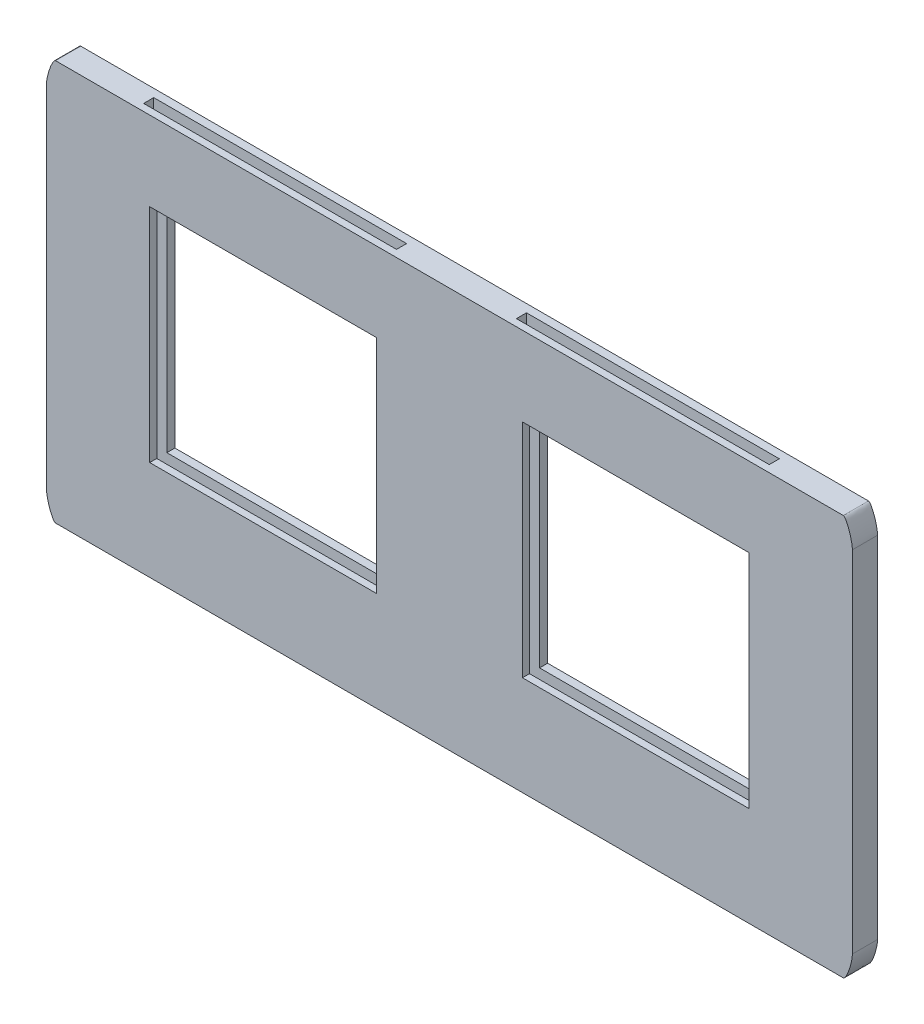
SolidWorks part; units mm, degrees
ref_plane "前视基准面" through (0, 0, 0) normal (0, 0, 1) x (1, 0, 0)
ref_plane "上视基准面" through (0, 0, 0) normal (0, 1, 0) x (1, 0, 0)
ref_plane "右视基准面" through (0, 0, 0) normal (1, 0, 0) x (0, 0, -1)
sketch "草图1" plane through (0, 0, 0) normal (0, 0, 1) x (1, 0, 0)
  line L1 (-80, 39.75) -> (80, 39.75)
  line L2 (-80, 39.75) -> (-80, -39.75)
  line L3 (-80, -39.75) -> (80, -39.75)
  line L4 (80, 39.75) -> (80, -39.75)
  line L5 (-80, 39.75) -> (80, -39.75) construction
  line L6 (-80, -39.75) -> (80, 39.75) construction
  point P0 (0, 0)
  dimension "D1" = 160
  dimension "D2" = 79.5
extrude "凸台-拉伸1" add sketch "草图1" along normal mid plane 5
sketch "草图2" plane through (0, 0, 2.5) normal (0, 0, 1) x (1, 0, 0)
  line L0 (0, 0) -> (0, -20.626) construction
  line L1 (-55, 12) -> (-19, 12) construction
  line L2 (-55, 12) -> (-55, -12) construction
  line L3 (-55, -12) -> (-19, -12) construction
  line L4 (-19, 12) -> (-19, -12) construction
  line L5 (-55, 12) -> (-19, -12) construction
  line L6 (-55, -12) -> (-19, 12) construction
  line L7 (55, -12) -> (19, 12) construction
  line L8 (55, 12) -> (19, -12) construction
  line L9 (19, 12) -> (19, -12) construction
  line L10 (55, -12) -> (19, -12) construction
  line L11 (55, 12) -> (55, -12) construction
  line L12 (55, 12) -> (19, 12) construction
  line L13 (-80, 39.75) -> (-80, -39.75) construction
  line L15 (-62, 25) -> (-12, 25) construction
  line L16 (-62, 25) -> (-62, -25) construction
  line L17 (-62, -25) -> (-12, -25) construction
  line L18 (-12, 25) -> (-12, -25) construction
  line L19 (-62, 25) -> (-12, -25) construction
  line L20 (-62, -25) -> (-12, 25) construction
  point P0 (-37, 0)
  point P12 (37, 0)
  point P15 (-37, 0)
  dimension "D1" = 36
  dimension "D2" = 24
  dimension "D3" = 43
  dimension "D4" = 50
sketch "草图3" plane through (0, 0, 2.5) normal (0, 0, 1) x (1, 0, 0)
  line L1 (-59.5, 24) -> (-14.5, 24)
  line L2 (-59.5, 24) -> (-59.5, -20)
  line L3 (-59.5, -20) -> (-14.5, -20)
  line L4 (-14.5, 24) -> (-14.5, -20)
  point P4 (-37, -20)
  dimension "D1" = 20
  dimension "D2" = 45
  dimension "D3" = 24
extrude "切除-拉伸1" cut sketch "草图3" against normal up to next
sketch "草图4" plane through (0, 39.75, 0) normal (0, 1, 0) x (1, 0, 0)
  line L1 (-62.1, 0.9) -> (-11.9, 0.9)
  line L2 (-62.1, 0.9) -> (-62.1, -1.1)
  line L3 (-62.1, -1.1) -> (-11.9, -1.1)
  line L4 (-11.9, 0.9) -> (-11.9, -1.1)
  line L5 (-62.1, 0.9) -> (-11.9, -1.1) construction
  line L6 (-62.1, -1.1) -> (-11.9, 0.9) construction
  point P0 (-37, -0.1)
  point P5 (-47, -6.8663)
  dimension "D1" = 2
  dimension "D2" = 50.2
  dimension "D3" = 0.1
extrude "切除-拉伸2" cut sketch "草图4" against normal offset from surface (64.75 mm away) 25 up to plane "上视基准面" offset beyond the face yes
mirror "镜向1" about plane through (0, 0, 0) normal (1, 0, 0) of "切除-拉伸1", "切除-拉伸2"
fillet "圆角1" radius 1.8 4 edges at (80, -39.75, 0) (80, 39.75, 0) (-80, -39.75, 0) (-80, 39.75, 0) second distance 5 conic rho 0.25 first distance on face at (0, -39.75, 0) first distance on face at (0, 39.75, 0)
